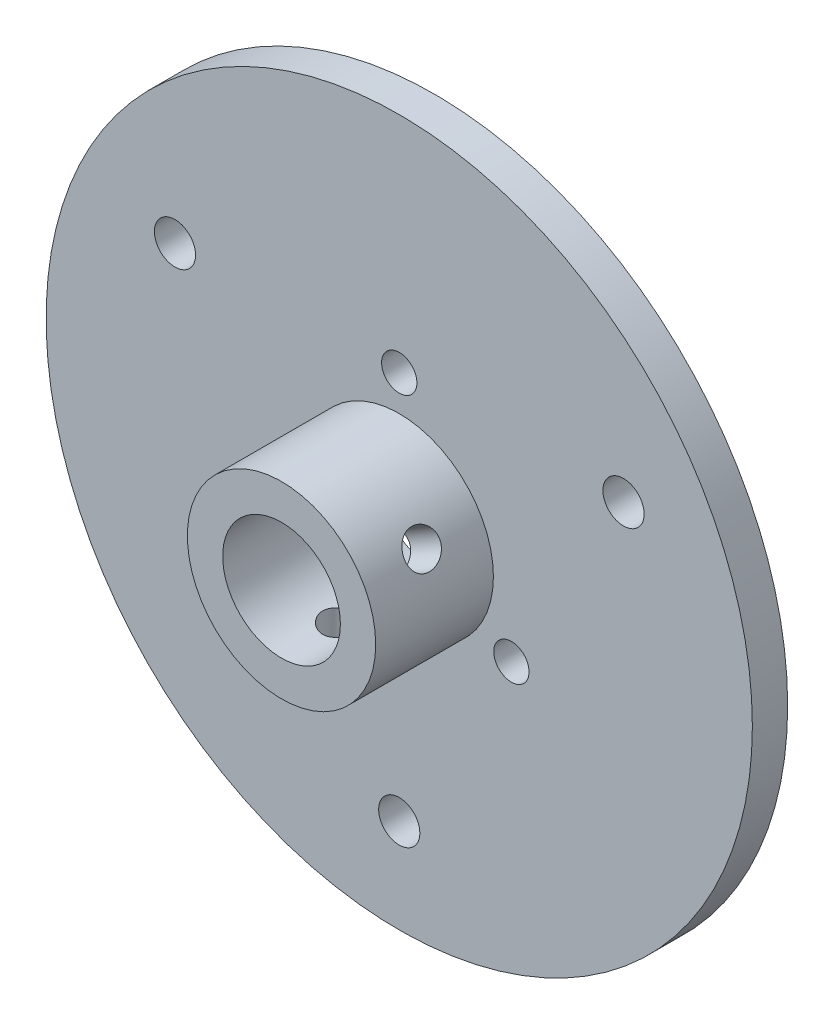
SolidWorks part; units mm, degrees
material "1060 Alloy"
ref_plane "Front Plane" through (0, 0, 0) normal (0, 0, 1) x (1, 0, 0)
ref_plane "Top Plane" through (0, 0, 0) normal (0, 1, 0) x (1, 0, 0)
ref_plane "Right Plane" through (0, 0, 0) normal (1, 0, 0) x (0, 0, -1)
sketch "Sketch2" plane through (0, 0, 0) normal (0, 0, 1) x (1, 0, 0)
  circle A0 centre (0, 0) radius 5
  circle A2 centre (0, 0) radius 22 construction
  circle A3 centre (0, 0) radius 30
  circle A4 centre (0, -22) radius 1.75
  circle A5 centre (-19.0526, 11) radius 1.75
  circle A6 centre (19.0526, 11) radius 1.75
  point P13 (0, 0)
  dimension "D1" = 3
  dimension "D2" = 44
  dimension "D3" = 3.5
  dimension "D4" = 10
  dimension "D5" = 60
extrude "Boss-Extrude1" add sketch "Sketch2" along normal blind 3
sketch "Sketch3" plane through (0, 0, 3) normal (0, 0, 1) x (1, 0, 0)
  circle A0 centre (0, 0) radius 8
  circle A1 centre (0, 0) radius 5
  dimension "D1" = 16
extrude "Boss-Extrude2" add sketch "Sketch3" along normal blind 10
sketch "Sketch4" plane through (0, 0, 3) normal (0, 0, 1) x (1, 0, 0)
  circle A10 centre (0, 11) radius 1.5
  circle A11 centre (9.5263, -5.5) radius 1.5
  circle A12 centre (-9.5263, -5.5) radius 1.5
  point P11 (0, 0)
  point P12 (0, 0)
  point P13 (0, 0)
  dimension "D1" = 3
  dimension "D2" = 3
  dimension "D3" = 11
extrude "Cut-Extrude2" cut sketch "Sketch4" against normal through all contours A12 | A11 | A10
sketch "Sketch12" plane through (0, 0, 0) normal (0, 1, 0) x (1, 0, 0)
  circle A0 centre (0, -8) radius 1.5
  dimension "D1" = 3
  dimension "D2" = 8
extrude "Cut-Extrude3" cut sketch "Sketch12" against normal blind 11.4938
pattern_circular "CirPattern1" count 3 every 120 about axis through (0, 0, 13) along (0, 0, 1) of "Cut-Extrude3"
